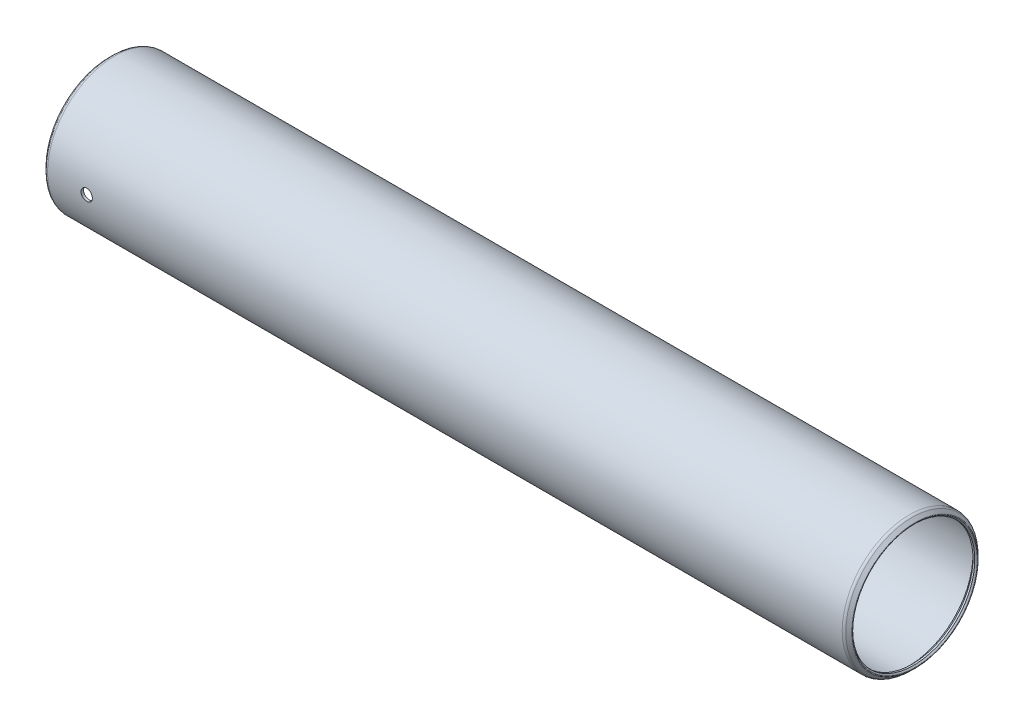
SolidWorks part; units mm, degrees
material "Cast Alloy Steel"
ref_plane "Front Plane" through (0, 0, 0) normal (0, 0, 1) x (1, 0, 0)
ref_plane "Top Plane" through (0, 0, 0) normal (0, 1, 0) x (1, 0, 0)
ref_plane "Right Plane" through (0, 0, 0) normal (1, 0, 0) x (0, 0, -1)
ref_plane "Plane1" through (168.1734, 0, 0) normal (1, 0, 0) x (0, 0, -1)
sketch "Sketch1" plane through (0, 0, 0) normal (0, 0, 1) x (1, 0, 0)
  line L0 (-0.6395, 13.1046) -> (-0.381, 12.846)
  line L1 (-0.381, 12.846) -> (0, 12.846)
  line L2 (0, 12.846) -> (0.762, 13.6081)
  line L3 (0.762, 13.6081) -> (167.4114, 13.6081)
  line L4 (167.4114, 13.6081) -> (168.1734, 12.846)
  line L5 (168.1734, 12.846) -> (168.5544, 12.846)
  line L6 (168.5544, 12.846) -> (168.8129, 13.1046)
  line L7 (168.8129, 13.2842) -> (168.1852, 13.9119)
  line L8 (167.6464, 14.1351) -> (0.527, 14.1351)
  line L9 (-0.0118, 13.9119) -> (-0.6395, 13.2842)
  line L10 (168.1734, 0) -> (0, 0) construction
  arc A0 (-0.6395, 13.2842) -> (-0.6395, 13.1046) centre (-0.5497, 13.1944) ccw
  arc A1 (168.8129, 13.1046) -> (168.8129, 13.2842) centre (168.7231, 13.1944) ccw
  arc A2 (168.1852, 13.9119) -> (167.6464, 14.1351) centre (167.6464, 13.3731) ccw
  arc A3 (0.527, 14.1351) -> (-0.0118, 13.9119) centre (0.527, 13.3731) ccw
revolve "Revolve1" add sketch "Sketch1" angle 360 about L10 reverse direction yes
sketch "Sketch2" plane through (0, 0, 0) normal (0, 0, 1) x (1, 0, 0)
  circle A0 centre (8.763, 0) radius 1.1938
extrude "Cut-Extrude1" cut sketch "Sketch2" along normal blind 14.1351
ref_plane "Plane2" through (84.0867, 0, 0) normal (1, 0, 0) x (0, 0, -1)
ref_plane "cp1 XY" through (84.0867, 0, 0) normal (1, 0, 0) x (0, 0, -1)
ref_plane "cp1 XZ" through (0, 14.1351, 0) normal (0, -1, 0) x (-1, 0, 0)
ref_plane "cp1 YZ" through (0, 0, 0) normal (0, 0, -1) x (-1, 0, 0)
ref_axis "cp1 X" through (84.0867, 14.1351, 80.9) along (0, 0, -1)
ref_axis "cp1 Y" through (84.0867, -50, 0) along (0, 1, 0)
ref_axis "cp1 Z" through (80.9, 14.1351, 0) along (-1, 0, 0)
sketch3d "cp1"
  point P0 (84.0867, 14.1351, 0)
ref_plane "cp2 XY" through (84.0867, 0, 0) normal (1, 0, 0) x (0, 0, -1)
ref_plane "cp2 XZ" through (0, 0, 0) normal (0, -1, 0) x (-1, 0, 0)
ref_plane "cp2 YZ" through (0, 0, -14.1351) normal (0, 0, -1) x (-1, 0, 0)
ref_axis "cp2 X" through (84.0867, 0, 80.9) along (0, 0, -1)
ref_axis "cp2 Y" through (84.0867, -50, -14.1351) along (0, 1, 0)
ref_axis "cp2 Z" through (80.9, 0, -14.1351) along (-1, 0, 0)
sketch3d "cp2"
  point P0 (84.0867, 0, -14.1351)
ref_plane "cp3 XY" through (84.0867, 0, 0) normal (1, 0, 0) x (0, 0, -1)
ref_plane "cp3 XZ" through (0, -14.1351, 0) normal (0, -1, 0) x (-1, 0, 0)
ref_plane "cp3 YZ" through (0, 0, 0) normal (0, 0, -1) x (-1, 0, 0)
ref_axis "cp3 X" through (84.0867, -14.1351, 80.9) along (0, 0, -1)
ref_axis "cp3 Y" through (84.0867, -50, 0) along (0, 1, 0)
ref_axis "cp3 Z" through (80.9, -14.1351, 0) along (-1, 0, 0)
sketch3d "cp3"
  point P0 (84.0867, -14.1351, 0)
ref_plane "cp4 XY" through (84.0867, 0, 0) normal (1, 0, 0) x (0, 0, -1)
ref_plane "cp4 XZ" through (0, 0, 0) normal (0, -1, 0) x (-1, 0, 0)
ref_plane "cp4 YZ" through (0, 0, 14.1351) normal (0, 0, -1) x (-1, 0, 0)
ref_axis "cp4 X" through (84.0867, 0, 80.9) along (0, 0, -1)
ref_axis "cp4 Y" through (84.0867, -50, 14.1351) along (0, 1, 0)
ref_axis "cp4 Z" through (80.9, 0, 14.1351) along (-1, 0, 0)
sketch3d "cp4"
  point P0 (84.0867, 0, 14.1351)
ref_plane "tube_front XY" through (0, 0, 0) normal (1, 0, 0) x (0, 0, -1)
ref_plane "tube_front XZ" through (0, 0, 0) normal (0, -1, 0) x (-1, 0, 0)
ref_plane "tube_front YZ" through (0, 0, 0) normal (0, 0, -1) x (-1, 0, 0)
ref_axis "tube_front X" through (0, 0, 80.9) along (0, 0, -1)
ref_axis "tube_front Y" through (0, -50, 0) along (0, 1, 0)
ref_axis "tube_front Z" through (80.9, 0, 0) along (-1, 0, 0)
sketch3d "tube_front"
  point P0 (0, 0, 0)
ref_plane "tube_rear XY" through (168.1734, 0, 0) normal (1, 0, 0) x (0, 0, -1)
ref_plane "tube_rear XZ" through (0, 0, 0) normal (0, -1, 0) x (-1, 0, 0)
ref_plane "tube_rear YZ" through (0, 0, 0) normal (0, 0, -1) x (-1, 0, 0)
ref_axis "tube_rear X" through (168.1734, 0, 80.9) along (0, 0, -1)
ref_axis "tube_rear Y" through (168.1734, -50, 0) along (0, 1, 0)
ref_axis "tube_rear Z" through (80.9, 0, 0) along (-1, 0, 0)
sketch3d "tube_rear"
  point P0 (168.1734, 0, 0)
